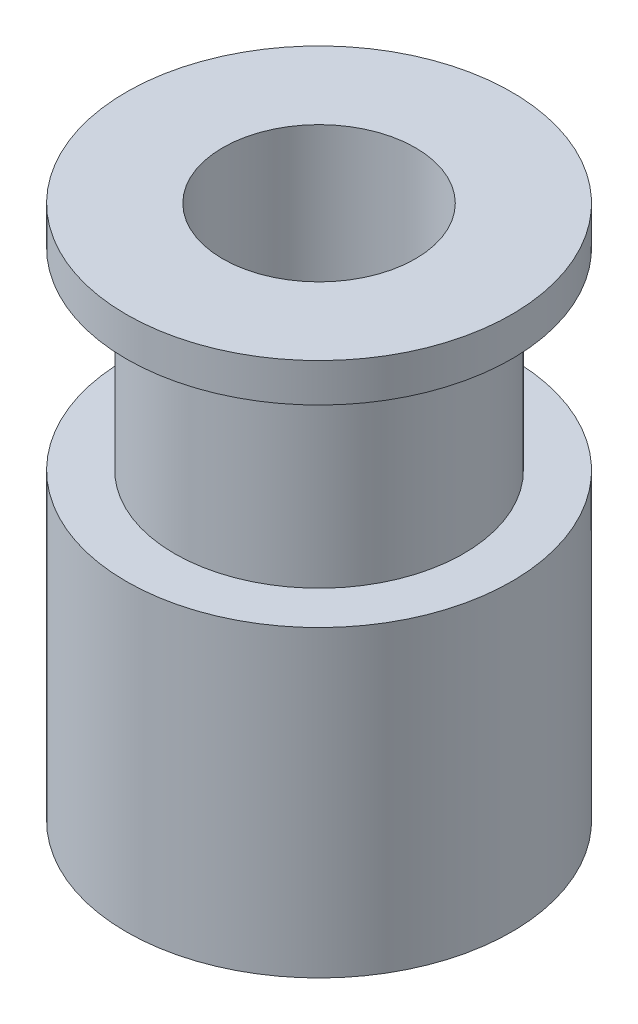
SolidWorks part; units mm, degrees
ref_plane "Plan de face" through (0, 0, 0) normal (0, 0, 1) x (1, 0, 0)
ref_plane "Plan de dessus" through (0, 0, 0) normal (0, 1, 0) x (1, 0, 0)
ref_plane "Plan de droite" through (0, 0, 0) normal (1, 0, 0) x (0, 0, -1)
sketch "Sketch1" plane through (0, 0, 0) normal (0, 1, 0) x (1, 0, 0)
  circle A0 centre (0, 0) radius 10
extrude "Boss-Extrude2" add sketch "Sketch1" along normal blind 10
sketch "Sketch5" plane through (0, 10, 0) normal (0, 1, 0) x (-1, 0, 0)
  circle A0 centre (0, 0) radius 1.5
extrude "Cut-Extrude3" cut sketch "Sketch5" against normal up to next
sketch "Sketch6" plane through (0, 10, 0) normal (0, 1, 0) x (-1, 0, 0)
  circle A0 centre (0, 0) radius 10
extrude "Boss-Extrude3" add sketch "Sketch6" along normal blind 5.75
sketch "Sketch7" plane through (0, 15.75, 0) normal (0, 1, 0) x (-1, 0, 0)
  circle A0 centre (0, 0) radius 5
extrude "Cut-Extrude4" cut sketch "Sketch7" against normal blind 5.75
sketch "Sketch8" plane through (0, 15.75, 0) normal (0, 1, 0) x (-1, 0, 0)
  circle A0 centre (0, 0) radius 7.5
extrude "Boss-Extrude4" add sketch "Sketch8" along normal blind 10
sketch "Sketch9" plane through (0, 25.75, 0) normal (0, 1, 0) x (-1, 0, 0)
  circle A0 centre (0, 0) radius 10
extrude "Boss-Extrude5" add sketch "Sketch9" along normal blind 2
sketch "Sketch10" plane through (0, 27.75, 0) normal (0, 1, 0) x (-1, 0, 0)
  circle A0 centre (0, 0) radius 5
extrude "Cut-Extrude5" cut sketch "Sketch10" against normal up to next
